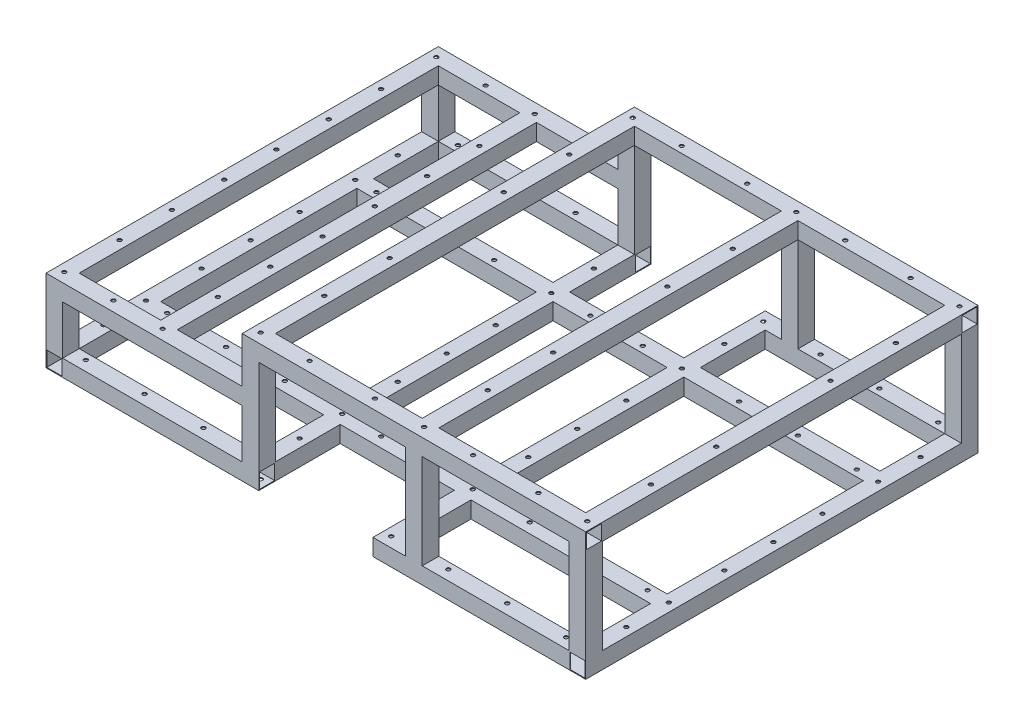
SolidWorks part; units mm, degrees
ref_plane "Front Plane" through (0, 0, 0) normal (0, 0, 1) x (1, 0, 0)
ref_plane "Top Plane" through (0, 0, 0) normal (0, 1, 0) x (1, 0, 0)
ref_plane "Right Plane" through (0, 0, 0) normal (1, 0, 0) x (0, 0, -1)
sketch "Sketch1" plane through (0, 0, 0) normal (0, 1, 0) x (1, 0, 0)
  line L0 (0, 0) -> (-415.7612, 0) construction
  line L1 (-387.3, -150) -> (387.3, -150)
  line L2 (-387.3, -150) -> (-387.3, -175.4)
  line L3 (-387.3, -175.4) -> (387.3, -175.4)
  line L4 (387.3, -150) -> (387.3, -175.4)
  line L9 (0, 0) -> (0, -321.173) construction
  line L10 (387.3, 150) -> (387.3, 175.4)
  line L11 (-387.3, 175.4) -> (387.3, 175.4)
  line L12 (-387.3, 150) -> (-387.3, 175.4)
  line L13 (-387.3, 150) -> (387.3, 150)
  point P7 (0, -175.4)
  dimension "D1" = 774.6
  dimension "D2" = 25.4
  dimension "D3" = 150
  dimension "D4" = 0
extrude "Boss-Extrude1" add sketch "Sketch1" along normal blind 25.4
sketch "Sketch4" plane through (-387.3, 0, 0) normal (-1, 0, 0) x (0, 0, 1)
  line L0 (-175.4, 25.4) -> (-150, 25.4) construction
  line L1 (-174.2, 24.2) -> (-151.2, 24.2)
  line L2 (-174.2, 24.2) -> (-174.2, 1.2)
  line L3 (-174.2, 1.2) -> (-151.2, 1.2)
  line L4 (-151.2, 24.2) -> (-151.2, 1.2)
  line L5 (-150, 25.4) -> (-150, 0) construction
  line L6 (-175.4, 0) -> (-150, 0) construction
  line L7 (-175.4, 25.4) -> (-175.4, 0) construction
  line L8 (0, 0) -> (0, 21.4103) construction
  line L9 (174.2, 1.2) -> (151.2, 1.2)
  line L10 (151.2, 24.2) -> (151.2, 1.2)
  line L11 (174.2, 24.2) -> (151.2, 24.2)
  line L12 (174.2, 24.2) -> (174.2, 1.2)
  dimension "D1" = 1.2
  dimension "D2" = 1.2
  dimension "D3" = 1.2
  dimension "D4" = 1.2
extrude "Cut-Extrude2" cut sketch "Sketch4" against normal up to next (774.6 mm away)
sketch "Sketch2" plane through (0, 0, 0) normal (0, -1, 0) x (1, 0, 0)
  line L0 (0, 0) -> (0, -349.2287) construction
  line L1 (412.7, 300) -> (387.3, 300)
  line L2 (412.7, 300) -> (412.7, -300)
  line L3 (412.7, -300) -> (387.3, -300)
  line L4 (387.3, 300) -> (387.3, -300)
  line L5 (0, 0) -> (432.1136, 0) construction
  line L6 (387.3, -150) -> (387.3, -175.4) construction
  line L7 (-387.3, 300) -> (-387.3, -300)
  line L8 (-412.7, -300) -> (-387.3, -300)
  line L9 (-412.7, 300) -> (-412.7, -300)
  line L10 (-412.7, 300) -> (-387.3, 300)
  point P10 (387.3, 0)
  dimension "D1" = 25.4
  dimension "D2" = 600
  dimension "D3" = 25.4
  dimension "D4" = 0
extrude "Boss-Extrude2" add sketch "Sketch2" against normal blind 25.4
sketch "Sketch3" plane through (0, 0, -300) normal (0, 0, -1) x (-1, 0, 0)
  line L0 (-387.3, 25.4) -> (-412.7, 25.4) construction
  line L1 (-411.5, 24.2) -> (-388.5, 24.2)
  line L2 (-411.5, 24.2) -> (-411.5, 1.2)
  line L3 (-411.5, 1.2) -> (-388.5, 1.2)
  line L4 (-388.5, 24.2) -> (-388.5, 1.2)
  line L5 (-387.3, 25.4) -> (-387.3, 0) construction
  line L6 (-387.3, 0) -> (-412.7, 0) construction
  line L7 (-412.7, 25.4) -> (-412.7, 0) construction
  line L8 (0, 0) -> (0, 119.739) construction
  line L9 (388.5, 24.2) -> (388.5, 1.2)
  line L10 (411.5, 1.2) -> (388.5, 1.2)
  line L11 (411.5, 24.2) -> (411.5, 1.2)
  line L12 (411.5, 24.2) -> (388.5, 24.2)
  point P10 (-400, 0)
  dimension "D1" = 1.2
  dimension "D2" = 1.2
  dimension "D3" = 1.2
  dimension "D4" = 1.2
extrude "Cut-Extrude1" cut sketch "Sketch3" against normal up to next
sketch "Sketch6" plane through (-387.3, 0, 0) normal (1, 0, 0) x (0, 0, -1)
  line L0 (300, 0) -> (175.4, 0) construction
  line L1 (300, 25.4) -> (274.6, 25.4)
  line L2 (300, 25.4) -> (300, 0)
  line L3 (300, 0) -> (274.6, 0)
  line L4 (274.6, 25.4) -> (274.6, 0)
  line L5 (0, 0) -> (0, 25.4) construction
  line L6 (150, 0) -> (-150, 0) construction
  line L7 (150, 25.4) -> (-150, 25.4) construction
  line L13 (-274.6, 25.4) -> (-274.6, 0)
  line L14 (-300, 0) -> (-274.6, 0)
  line L15 (-300, 25.4) -> (-300, 0)
  line L16 (-300, 25.4) -> (-274.6, 25.4)
  dimension "D1" = 25.4
extrude "Boss-Extrude3" add sketch "Sketch6" along normal blind 300
sketch "Sketch7" plane through (387.3, 0, 0) normal (-1, 0, 0) x (0, 0, 1)
  line L0 (-175.4, 25.4) -> (-300, 25.4) construction
  line L1 (-300, 0) -> (-274.6, 0)
  line L2 (-300, 0) -> (-300, 25.4)
  line L3 (-300, 25.4) -> (-274.6, 25.4)
  line L4 (-274.6, 0) -> (-274.6, 25.4)
  line L10 (0, 0) -> (0, 25.4) construction
  line L11 (150, 0) -> (-150, 0) construction
  line L12 (150, 25.4) -> (-150, 25.4) construction
  line L13 (274.6, 0) -> (274.6, 25.4)
  line L14 (300, 25.4) -> (274.6, 25.4)
  line L15 (300, 0) -> (300, 25.4)
  line L16 (300, 0) -> (274.6, 0)
  dimension "D1" = 25.4
extrude "Boss-Extrude4" add sketch "Sketch7" along normal blind 300
ref_plane "Plane1" through (0, 0, 0) normal (1, 0, 0) x (0, 0, -1)
sketch "Sketch8" plane through (0, 0, 0) normal (1, 0, 0) x (0, 0, -1)
  line L4 (-275.8, 24.2) -> (-298.8, 24.2)
  line L5 (-298.8, 24.2) -> (-298.8, 1.2)
  line L6 (-298.8, 1.2) -> (-275.8, 1.2)
  line L7 (-275.8, 1.2) -> (-275.8, 24.2)
  line L8 (-274.6, 25.4) -> (-300, 25.4)
  line L9 (-300, 25.4) -> (-300, 0)
  line L10 (-300, 0) -> (-274.6, 0)
  line L11 (-274.6, 0) -> (-274.6, 25.4)
  line L12 (-274.6, 25.4) -> (-300, 25.4)
  line L13 (-300, 25.4) -> (-300, 0)
  line L14 (-300, 0) -> (-274.6, 0)
  line L15 (-274.6, 0) -> (-274.6, 25.4)
  line L16 (300, 0) -> (300, 25.4)
  line L17 (300, 25.4) -> (274.6, 25.4)
  line L18 (274.6, 25.4) -> (274.6, 0)
  line L19 (274.6, 0) -> (300, 0)
  line L20 (300, 0) -> (300, 25.4)
  line L21 (300, 25.4) -> (274.6, 25.4)
  line L22 (274.6, 25.4) -> (274.6, 0)
  line L23 (274.6, 0) -> (300, 0)
  line L24 (298.8, 1.2) -> (298.8, 24.2)
  line L25 (298.8, 24.2) -> (275.8, 24.2)
  line L26 (275.8, 24.2) -> (275.8, 1.2)
  line L27 (275.8, 1.2) -> (298.8, 1.2)
  dimension "D1" = 0
  dimension "D2" = 0
  dimension "D3" = 1.2
  dimension "D4" = 1.2
extrude "Cut-Extrude4" cut sketch "Sketch8" against normal up to surface (388.5 mm away) and the other way up to vertex (388.5 mm away) contours L24 L25 L26 L27 | L7 L4 L5 L6 up to face at (-388.5, 12.7, 0) other way up to point (388.5, 1.2, 300)
sketch "Sketch9" plane through (0, 0, -274.6) normal (0, 0, 1) x (1, 0, 0)
  line L0 (-87.3, 25.4) -> (-387.3, 25.4) construction
  line L1 (-87.3, 0) -> (-112.7, 0)
  line L2 (-87.3, 0) -> (-87.3, 25.4)
  line L3 (-87.3, 25.4) -> (-112.7, 25.4)
  line L4 (-112.7, 0) -> (-112.7, 25.4)
  line L5 (-87.3, 0) -> (87.3, 0) construction
  line L6 (-87.3, 25.4) -> (87.3, 25.4) construction
  line L7 (0, 25.4) -> (0, 0) construction
  line L12 (-88.5, 1.2) -> (-111.5, 1.2)
  line L13 (-111.5, 1.2) -> (-111.5, 24.2)
  line L14 (-88.5, 24.2) -> (-111.5, 24.2)
  line L15 (-88.5, 1.2) -> (-88.5, 24.2)
  line L16 (88.5, 1.2) -> (88.5, 24.2)
  line L17 (88.5, 24.2) -> (111.5, 24.2)
  line L18 (87.3, 25.4) -> (112.7, 25.4)
  line L19 (87.3, 0) -> (87.3, 25.4)
  line L20 (111.5, 1.2) -> (111.5, 24.2)
  line L21 (88.5, 1.2) -> (111.5, 1.2)
  line L22 (112.7, 0) -> (112.7, 25.4)
  line L23 (87.3, 0) -> (112.7, 0)
  dimension "D1" = 25.4
  dimension "D2" = 1.2
extrude "Boss-Extrude5" add sketch "Sketch9" along normal up to surface (550.4 mm away) up to face at (-237.9, 12.7, 275.8)
sketch "Sketch11" plane through (0, 25.4, 0) normal (0, 1, 0) x (1, 0, 0)
  line L0 (-412.7, 0) -> (0, 0) construction
  line L1 (-412.7, 300) -> (-387.3, 300)
  line L2 (-412.7, 300) -> (-412.7, 274.6)
  line L3 (-412.7, 274.6) -> (-387.3, 274.6)
  line L4 (-387.3, 300) -> (-387.3, 274.6)
  line L5 (-412.7, -300) -> (-412.7, 300) construction
  line L7 (-411.5, 298.8) -> (-388.5, 298.8)
  line L8 (-388.5, 298.8) -> (-388.5, 275.8)
  line L9 (-411.5, 275.8) -> (-388.5, 275.8)
  line L10 (-411.5, 298.8) -> (-411.5, 275.8)
  line L11 (-411.5, -298.8) -> (-411.5, -275.8)
  line L12 (-411.5, -275.8) -> (-388.5, -275.8)
  line L13 (-388.5, -298.8) -> (-388.5, -275.8)
  line L14 (-411.5, -298.8) -> (-388.5, -298.8)
  line L15 (-387.3, -300) -> (-387.3, -274.6)
  line L16 (-412.7, -274.6) -> (-387.3, -274.6)
  line L17 (-412.7, -300) -> (-412.7, -274.6)
  line L18 (-412.7, -300) -> (-387.3, -300)
  dimension "D1" = 1.2
extrude "Boss-Extrude6" add sketch "Sketch11" along normal blind 74.6
sketch "Sketch12" plane through (0, 25.4, 0) normal (0, 1, 0) x (1, 0, 0)
  line L0 (-88.5, 298.8) -> (-111.5, 298.8)
  line L1 (-87.3, 300) -> (-112.7, 300)
  line L2 (-87.3, 300) -> (-87.3, 274.6)
  line L3 (-87.3, 274.6) -> (-112.7, 274.6)
  line L4 (-112.7, 300) -> (-112.7, 274.6)
  line L5 (-111.5, 298.8) -> (-111.5, 275.8)
  line L6 (-88.5, 275.8) -> (-111.5, 275.8)
  line L7 (-88.5, 298.8) -> (-88.5, 275.8)
  line L8 (-112.7, 0) -> (412.7, 0) construction
  line L10 (-112.7, -150) -> (-112.7, 150) construction
  line L11 (412.7, 300) -> (412.7, -300) construction
  line L12 (150, 0) -> (150, 300) construction
  line L13 (87.3, 300) -> (412.7, 300) construction
  line L14 (-88.5, -298.8) -> (-88.5, -275.8)
  line L15 (-88.5, -275.8) -> (-111.5, -275.8)
  line L16 (-111.5, -298.8) -> (-111.5, -275.8)
  line L17 (-112.7, -300) -> (-112.7, -274.6)
  line L18 (-87.3, -274.6) -> (-112.7, -274.6)
  line L19 (-87.3, -300) -> (-87.3, -274.6)
  line L20 (-87.3, -300) -> (-112.7, -300)
  line L21 (-88.5, -298.8) -> (-111.5, -298.8)
  line L22 (388.5, -298.8) -> (411.5, -298.8)
  line L23 (387.3, -300) -> (412.7, -300)
  line L24 (387.3, -300) -> (387.3, -274.6)
  line L25 (387.3, -274.6) -> (412.7, -274.6)
  line L26 (412.7, -300) -> (412.7, -274.6)
  line L27 (411.5, -298.8) -> (411.5, -275.8)
  line L28 (388.5, -275.8) -> (411.5, -275.8)
  line L29 (388.5, -298.8) -> (388.5, -275.8)
  line L30 (388.5, 298.8) -> (388.5, 275.8)
  line L31 (388.5, 275.8) -> (411.5, 275.8)
  line L32 (411.5, 298.8) -> (411.5, 275.8)
  line L33 (412.7, 300) -> (412.7, 274.6)
  line L34 (387.3, 274.6) -> (412.7, 274.6)
  line L35 (387.3, 300) -> (387.3, 274.6)
  line L36 (387.3, 300) -> (412.7, 300)
  line L37 (388.5, 298.8) -> (411.5, 298.8)
  line L38 (112.7, 274.6) -> (387.3, 274.6) construction
  line L39 (137.3, 300) -> (162.7, 300)
  line L40 (137.3, 300) -> (137.3, 274.6)
  line L41 (137.3, 274.6) -> (162.7, 274.6)
  line L42 (162.7, 300) -> (162.7, 274.6)
  line L47 (138.5, 298.8) -> (161.5, 298.8)
  line L48 (161.5, 298.8) -> (161.5, 275.8)
  line L49 (138.5, 275.8) -> (161.5, 275.8)
  line L50 (138.5, 298.8) -> (138.5, 275.8)
  line L51 (138.5, -298.8) -> (138.5, -275.8)
  line L52 (138.5, -275.8) -> (161.5, -275.8)
  line L53 (161.5, -298.8) -> (161.5, -275.8)
  line L54 (138.5, -298.8) -> (161.5, -298.8)
  line L55 (162.7, -300) -> (162.7, -274.6)
  line L56 (137.3, -274.6) -> (162.7, -274.6)
  line L57 (137.3, -300) -> (137.3, -274.6)
  line L58 (137.3, -300) -> (162.7, -300)
  line L59 (87.3, 175.4) -> (87.3, 300) construction
  dimension "D2" = 50
  dimension "D3" = 25.4
  dimension "D1" = 1.2
  dimension "D4" = 1.2
extrude "Boss-Extrude7" add sketch "Sketch12" along normal blind 144.6
sketch "Sketch13" plane through (0, 170, 0) normal (0, 1, 0) x (1, 0, 0)
  line L0 (-87.3, 274.6) -> (-87.3, -274.6) construction
  line L1 (-112.7, -300) -> (412.7, -300)
  line L2 (-112.7, -300) -> (-112.7, -274.6)
  line L3 (-112.7, -274.6) -> (412.7, -274.6)
  line L4 (412.7, -300) -> (412.7, -274.6)
  line L5 (-87.3, 0) -> (0, 0) construction
  line L6 (412.7, 300) -> (412.7, 274.6)
  line L7 (-112.7, 274.6) -> (412.7, 274.6)
  line L8 (-112.7, 300) -> (-112.7, 274.6)
  line L9 (-112.7, 300) -> (412.7, 300)
extrude "Boss-Extrude9" add sketch "Sketch13" along normal blind 25.4
sketch "Sketch14" plane through (-112.7, 0, 0) normal (-1, 0, 0) x (0, 0, 1)
  line L0 (-300, 195.4) -> (-274.6, 195.4) construction
  line L1 (-298.8, 194.2) -> (-275.8, 194.2)
  line L2 (-298.8, 194.2) -> (-298.8, 171.2)
  line L3 (-298.8, 171.2) -> (-275.8, 171.2)
  line L4 (-275.8, 194.2) -> (-275.8, 171.2)
  line L5 (-300, 195.4) -> (-300, 25.4) construction
  line L6 (-274.6, 195.4) -> (-274.6, 25.4) construction
  line L7 (-300, 170) -> (-274.6, 170) construction
  line L8 (-274.6, 170) -> (274.6, 170) construction
  line L9 (274.6, 195.4) -> (274.6, 25.4) construction
  line L10 (0, 170) -> (0, 204.2) construction
  line L11 (300, 170) -> (274.6, 170) construction
  line L12 (275.8, 194.2) -> (275.8, 171.2)
  line L13 (298.8, 171.2) -> (275.8, 171.2)
  line L14 (298.8, 194.2) -> (298.8, 171.2)
  line L15 (298.8, 194.2) -> (275.8, 194.2)
  dimension "D1" = 1.2
  dimension "D2" = 1.2
  dimension "D3" = 1.2
  dimension "D4" = 25.4
  dimension "D5" = 1.2
extrude "Cut-Extrude5" cut sketch "Sketch14" against normal up to surface (525.4 mm away) up to face at (412.7, 104.05, 0)
sketch "Sketch15" plane through (0, 0, -274.6) normal (0, 0, 1) x (1, 0, 0)
  line L0 (-112.7, 195.4) -> (412.7, 195.4) construction
  line L1 (-112.7, 195.4) -> (-87.3, 195.4)
  line L2 (-112.7, 195.4) -> (-112.7, 170)
  line L3 (-112.7, 170) -> (-87.3, 170)
  line L4 (-87.3, 195.4) -> (-87.3, 170)
  line L5 (137.3, 170) -> (162.7, 170)
  line L6 (137.3, 170) -> (137.3, 195.4)
  line L7 (137.3, 195.4) -> (162.7, 195.4)
  line L8 (162.7, 170) -> (162.7, 195.4)
  line L9 (-111.5, 194.2) -> (-88.5, 194.2)
  line L10 (387.3, 170) -> (412.7, 170)
  line L11 (387.3, 170) -> (387.3, 195.4)
  line L12 (387.3, 195.4) -> (412.7, 195.4)
  line L13 (412.7, 170) -> (412.7, 195.4)
  line L14 (-88.5, 194.2) -> (-88.5, 171.2)
  line L15 (-111.5, 171.2) -> (-88.5, 171.2)
  line L16 (-111.5, 194.2) -> (-111.5, 171.2)
  line L17 (138.5, 171.2) -> (161.5, 171.2)
  line L18 (161.5, 171.2) -> (161.5, 194.2)
  line L19 (138.5, 194.2) -> (161.5, 194.2)
  line L20 (138.5, 171.2) -> (138.5, 194.2)
  line L21 (388.5, 171.2) -> (411.5, 171.2)
  line L22 (411.5, 171.2) -> (411.5, 194.2)
  line L23 (388.5, 194.2) -> (411.5, 194.2)
  line L24 (388.5, 171.2) -> (388.5, 194.2)
  dimension "D1" = 1.2
extrude "Boss-Extrude10" add sketch "Sketch15" along normal up to surface (549.2 mm away) up to face at (100, 12.7, 274.6)
sketch "Sketch16" plane through (-412.7, 0, 0) normal (-1, 0, 0) x (0, 0, 1)
  line L0 (275.8, 101.2) -> (298.8, 101.2)
  line L1 (274.6, 100) -> (300, 100)
  line L2 (274.6, 100) -> (274.6, 125.4)
  line L3 (274.6, 125.4) -> (300, 125.4)
  line L4 (300, 100) -> (300, 125.4)
  line L5 (298.8, 101.2) -> (298.8, 124.2)
  line L6 (275.8, 124.2) -> (298.8, 124.2)
  line L7 (275.8, 101.2) -> (275.8, 124.2)
  line L8 (-274.6, 100) -> (274.6, 100) construction
  line L9 (0, 100) -> (0, 0) construction
  line L11 (300, 0) -> (-300, 0) construction
  line L12 (-275.8, 101.2) -> (-275.8, 124.2)
  line L13 (-275.8, 124.2) -> (-298.8, 124.2)
  line L14 (-298.8, 101.2) -> (-298.8, 124.2)
  line L15 (-300, 100) -> (-300, 125.4)
  line L16 (-274.6, 125.4) -> (-300, 125.4)
  line L17 (-274.6, 100) -> (-274.6, 125.4)
  line L18 (-274.6, 100) -> (-300, 100)
  line L19 (-275.8, 101.2) -> (-298.8, 101.2)
  dimension "D1" = 25.4
  dimension "D2" = 25.4
  dimension "D3" = 1.2
extrude "Boss-Extrude11" add sketch "Sketch16" against normal up to surface (300 mm away) up to face at (-112.7, 182.7, -287.3)
sketch "Sketch17" plane through (0, 0, 274.6) normal (0, 0, -1) x (-1, 0, 0)
  line L0 (112.7, 100) -> (387.3, 100) construction
  line L1 (387.3, 100) -> (412.7, 100)
  line L2 (387.3, 100) -> (387.3, 125.4)
  line L3 (387.3, 125.4) -> (412.7, 125.4)
  line L4 (412.7, 100) -> (412.7, 125.4)
  line L5 (250, 100) -> (250, 125.4) construction
  line L6 (112.7, 125.4) -> (412.7, 125.4) construction
  line L7 (238.5, 124.2) -> (261.5, 124.2)
  line L8 (237.3, 125.4) -> (262.7, 125.4)
  line L9 (237.3, 125.4) -> (237.3, 100)
  line L10 (237.3, 100) -> (262.7, 100)
  line L11 (262.7, 125.4) -> (262.7, 100)
  line L12 (261.5, 124.2) -> (261.5, 101.2)
  line L13 (238.5, 101.2) -> (261.5, 101.2)
  line L14 (238.5, 124.2) -> (238.5, 101.2)
  line L16 (388.5, 101.2) -> (411.5, 101.2)
  line L17 (411.5, 101.2) -> (411.5, 124.2)
  line L18 (388.5, 124.2) -> (411.5, 124.2)
  line L19 (388.5, 101.2) -> (388.5, 124.2)
  dimension "D1" = 25.4
  dimension "D2" = 12.7
  dimension "D3" = 1.2
  dimension "D4" = 1.2
extrude "Boss-Extrude12" add sketch "Sketch17" along normal up to surface (549.2 mm away) up to face at (25, 182.7, -274.6)
sketch "Sketch18" plane through (0, 25.4, 0) normal (0, 1, 0) x (1, 0, 0)
  line L0 (162.7, 274.6) -> (387.3, 274.6) construction
  line L1 (387.3, 300) -> (387.3, 274.6) construction
  line L2 (112.7, 274.6) -> (137.3, 274.6) construction
  line L3 (87.3, 175.4) -> (87.3, 300) construction
  line L4 (387.3, -150) -> (387.3, 150) construction
  line L5 (112.7, 150) -> (387.3, 150) construction
  line L6 (87.3, -150) -> (87.3, 150) construction
  line L7 (412.7, 0) -> (0, 0) construction
  line L8 (412.7, 274.6) -> (412.7, -274.6) construction
  line L9 (0, 0) -> (0, 303.2716) construction
  line L10 (87.3, 300) -> (137.3, 300) construction
  line L11 (387.3, 175.4) -> (387.3, 274.6) construction
  line L12 (388.5, 300) -> (411.5, 300) construction
  line L13 (411.5, 300) -> (388.5, 300) construction
  line L14 (87.3, 300) -> (412.7, 300) construction
  line L15 (-87.3, 150) -> (87.3, 150) construction
  circle A0 centre (367.3, 284.6) radius 3
  circle A1 centre (277.3, 284.6) radius 3
  circle A2 centre (187.3, 284.6) radius 3
  circle A3 centre (99.8, 284.6) radius 3
  circle A4 centre (367.3, 160) radius 3
  circle A5 centre (277.3, 160) radius 3
  circle A6 centre (187.3, 160) radius 3
  circle A7 centre (99.8, 160) radius 3
  circle A8 centre (99.8, 225) radius 3
  circle A9 centre (399.8, 225) radius 3
  circle A11 centre (399.8, 0) radius 3
  circle A12 centre (399.8, 75) radius 3
  circle A13 centre (99.8, 0) radius 3
  circle A14 centre (99.8, 75) radius 3
  circle A15 centre (399.8, 160) radius 3
  circle A16 centre (40, 160) radius 3
  circle A17 centre (-40, 160) radius 3
  circle A18 centre (-399.8, 160) radius 3
  circle A19 centre (-99.8, 75) radius 3
  circle A20 centre (-99.8, 0) radius 3
  circle A21 centre (-399.8, 75) radius 3
  circle A22 centre (-399.8, 0) radius 3
  circle A23 centre (-399.8, 225) radius 3
  circle A24 centre (-99.8, 225) radius 3
  circle A25 centre (-99.8, 160) radius 3
  circle A26 centre (-187.3, 160) radius 3
  circle A27 centre (-277.3, 160) radius 3
  circle A28 centre (-367.3, 160) radius 3
  circle A29 centre (-99.8, 284.6) radius 3
  circle A30 centre (-187.3, 284.6) radius 3
  circle A31 centre (-277.3, 284.6) radius 3
  circle A32 centre (-367.3, 284.6) radius 3
  circle A33 centre (-367.3, -284.6) radius 3
  circle A34 centre (-277.3, -284.6) radius 3
  circle A35 centre (-187.3, -284.6) radius 3
  circle A36 centre (-99.8, -284.6) radius 3
  circle A37 centre (-367.3, -160) radius 3
  circle A38 centre (-277.3, -160) radius 3
  circle A39 centre (-187.3, -160) radius 3
  circle A40 centre (-99.8, -160) radius 3
  circle A41 centre (-99.8, -225) radius 3
  circle A42 centre (-399.8, -225) radius 3
  circle A43 centre (-399.8, -75) radius 3
  circle A44 centre (-99.8, -75) radius 3
  circle A45 centre (-399.8, -160) radius 3
  circle A46 centre (-40, -160) radius 3
  circle A47 centre (40, -160) radius 3
  circle A48 centre (399.8, -160) radius 3
  circle A49 centre (99.8, -75) radius 3
  circle A50 centre (399.8, -75) radius 3
  circle A51 centre (399.8, -225) radius 3
  circle A52 centre (99.8, -225) radius 3
  circle A53 centre (99.8, -160) radius 3
  circle A54 centre (187.3, -160) radius 3
  circle A55 centre (277.3, -160) radius 3
  circle A56 centre (367.3, -160) radius 3
  circle A57 centre (99.8, -284.6) radius 3
  circle A58 centre (187.3, -284.6) radius 3
  circle A59 centre (277.3, -284.6) radius 3
  circle A60 centre (367.3, -284.6) radius 3
  dimension "D1" = 10
  dimension "D5" = 6
  dimension "D6" = 6
  dimension "D7" = 10
  dimension "D9" = 6
  dimension "D10" = 6
  dimension "D13" = 6
  dimension "D14" = 6
  dimension "D15" = 6
  dimension "D22" = 6
  dimension "D27" = 6
  dimension "D28" = 6
  dimension "D29" = 12.5
  dimension "D30" = 75
  dimension "D33" = 6
  dimension "D34" = 6
  dimension "D35" = 6
  dimension "D36" = 6
  dimension "D43" = 6
  dimension "D44" = 12.5
  dimension "D46" = 6
  dimension "D2" = 20
  dimension "D3" = 10
  dimension "D4" = 110
  dimension "D8" = 200
  dimension "D11" = 10
  dimension "D12" = 12.5
  dimension "D16" = 20
  dimension "D17" = 10
  dimension "D18" = 110
  dimension "D19" = 10
  dimension "D20" = 10
  dimension "D21" = 200
  dimension "D23" = 10
  dimension "D24" = 12.5
  dimension "D25" = 12.5
  dimension "D26" = 75
  dimension "D31" = 12.5
  dimension "D32" = 300
  dimension "D37" = 12.5
  dimension "D38" = 12.5
  dimension "D39" = 225
  dimension "D40" = 300
  dimension "D41" = 225
  dimension "D42" = 12.5
  dimension "D45" = 10
  dimension "D47" = 10
  dimension "D48" = 40
extrude "Cut-Extrude6" cut sketch "Sketch18" against normal up to surface (25.4 mm away) up to face at (0, 0, 0)
sketch "Sketch20" plane through (0, 195.4, 0) normal (0, 1, 0) x (1, 0, 0)
  line L0 (387.3, 0) -> (162.7, 0) construction
  line L1 (387.3, -274.6) -> (387.3, 274.6) construction
  line L2 (162.7, -274.6) -> (162.7, 274.6) construction
  line L3 (412.7, 300) -> (-112.7, 300) construction
  line L4 (150, 300) -> (150, -300) construction
  line L5 (-112.7, -300) -> (412.7, -300) construction
  line L6 (275, 274.6) -> (275, 0) construction
  line L7 (162.7, 274.6) -> (387.3, 274.6) construction
  line L8 (275, 137.3) -> (387.3, 137.3) construction
  circle A0 centre (399.8, 284.6) radius 3
  circle A2 centre (399.8, 187.3) radius 3
  circle A3 centre (325, 284.6) radius 3
  circle A4 centre (225, 284.6) radius 3
  circle A5 centre (150.2, 187.3) radius 3
  circle A6 centre (150.2, 284.6) radius 3
  circle A7 centre (150.2, 87.3) radius 3
  circle A8 centre (399.8, 87.3) radius 3
  circle A9 centre (399.8, -87.3) radius 3
  circle A10 centre (150.2, -87.3) radius 3
  circle A11 centre (150.2, -284.6) radius 3
  circle A12 centre (150.2, -187.3) radius 3
  circle A13 centre (225, -284.6) radius 3
  circle A14 centre (325, -284.6) radius 3
  circle A15 centre (399.8, -187.3) radius 3
  circle A16 centre (399.8, -284.6) radius 3
  circle A17 centre (-99.8, -284.6) radius 3
  circle A18 centre (-99.8, -187.3) radius 3
  circle A19 centre (-25, -284.6) radius 3
  circle A20 centre (75, -284.6) radius 3
  circle A21 centre (-99.8, -87.3) radius 3
  circle A22 centre (-99.8, 87.3) radius 3
  circle A23 centre (75, 284.6) radius 3
  circle A24 centre (-25, 284.6) radius 3
  circle A25 centre (-99.8, 187.3) radius 3
  circle A26 centre (-99.8, 284.6) radius 3
  dimension "D1" = 6
  dimension "D6" = 6
  dimension "D7" = 6
  dimension "D2" = 10
  dimension "D3" = 12.5
  dimension "D4" = 10
  dimension "D5" = 50
  dimension "D8" = 50
  dimension "D9" = 12.5
extrude "Cut-Extrude7" cut sketch "Sketch20" against normal up to next (1.2 mm away)
sketch "Sketch21" plane through (0, 125.4, 0) normal (0, 1, 0) x (1, 0, 0)
  line L0 (-262.7, 0) -> (-387.3, 0) construction
  line L1 (-262.7, 274.6) -> (-262.7, -274.6) construction
  line L2 (-387.3, 274.6) -> (-387.3, -274.6) construction
  line L3 (-325, 274.6) -> (-325, 0) construction
  line L4 (-262.7, 274.6) -> (-387.3, 274.6) construction
  line L5 (-412.7, -300) -> (-412.7, 300) construction
  line L6 (-112.7, 300) -> (-412.7, 300) construction
  circle A0 centre (-400.2, 284.6) radius 3
  circle A1 centre (-324.995, 284.6) radius 3
  circle A2 centre (-400.2, 200) radius 3
  circle A3 centre (-400.2, 120) radius 3
  circle A4 centre (-400.2, 40) radius 3
  circle A5 centre (-249.8, 40) radius 3
  circle A6 centre (-249.8, 120) radius 3
  circle A7 centre (-249.8, 200) radius 3
  circle A8 centre (-249.8, 284.6) radius 3
  circle A9 centre (-249.8, -284.6) radius 3
  circle A10 centre (-249.8, -200) radius 3
  circle A11 centre (-249.8, -120) radius 3
  circle A12 centre (-400.2, -40) radius 3
  circle A13 centre (-400.2, -120) radius 3
  circle A14 centre (-400.2, -200) radius 3
  circle A15 centre (-324.995, -284.6) radius 3
  circle A16 centre (-400.2, -284.6) radius 3
  circle A17 centre (-249.8, -40) radius 3
  dimension "D1" = 12.5
  dimension "D3" = 6
  dimension "D4" = 6
  dimension "D5" = 10
  dimension "D8" = 6
  dimension "D9" = 6
  dimension "D13" = 12.5
  dimension "D14" = 6
  dimension "D2" = 10
  dimension "D6" = 0.01
  dimension "D7" = 12.5
  dimension "D10" = 12.5
  dimension "D11" = 100
  dimension "D12" = 120
  dimension "D15" = 40
extrude "Cut-Extrude8" cut sketch "Sketch21" against normal up to next
equation "\"thi\"=1.2"
equation "\"D5@Sketch14\"=\"thi\""
equation "\"D2@Sketch14\"=\"thi\""
equation "\"D3@Sketch14\"=\"thi\""
equation "\"D1@Sketch14\"=\"thi\""
